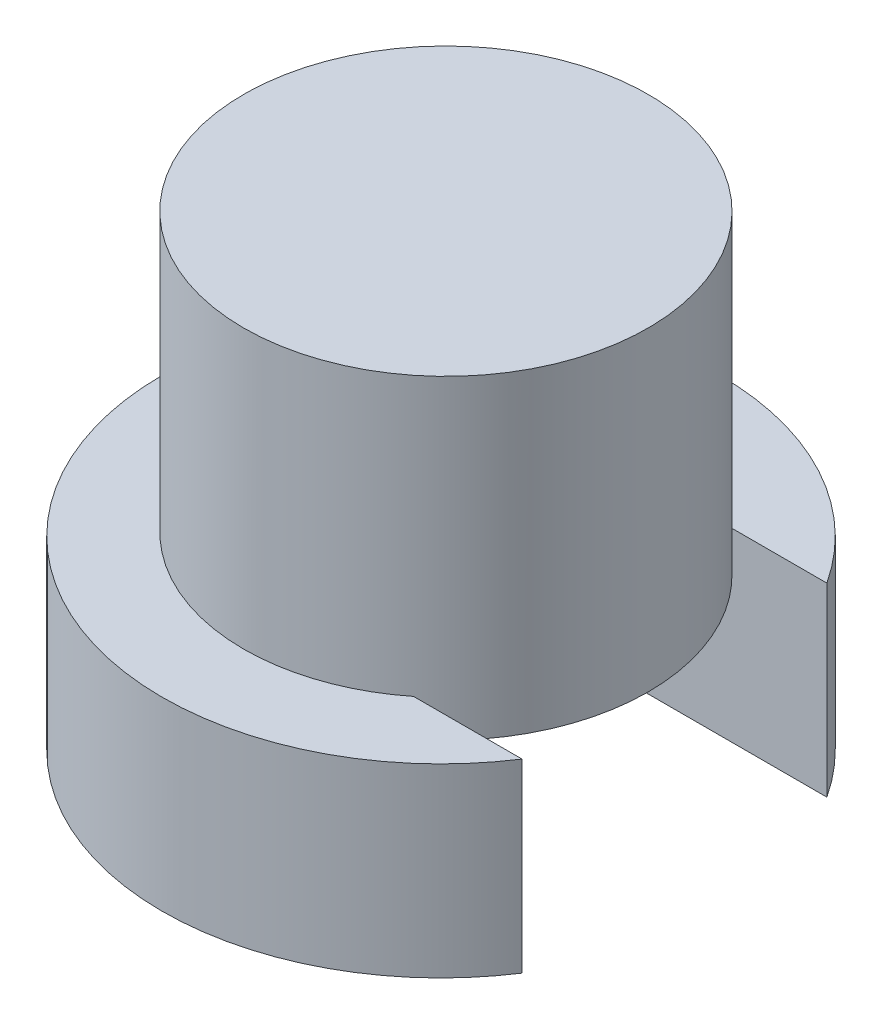
SolidWorks part; units mm, degrees
ref_plane "Front Plane" through (0, 0, 0) normal (0, 0, 1) x (1, 0, 0)
ref_plane "Top Plane" through (0, 0, 0) normal (0, 1, 0) x (1, 0, 0)
ref_plane "Right Plane" through (0, 0, 0) normal (1, 0, 0) x (0, 0, -1)
sketch "Sketch1" plane through (0, 0, 0) normal (0, 1, 0) x (1, 0, 0)
  line L1 (-21.3537, 0) -> (49.3226, 0)
  line L2 (-21.3537, 0) -> (-21.3537, 32.8817)
  line L3 (-21.3537, 32.8817) -> (49.3226, 32.8817)
  line L4 (49.3226, 0) -> (49.3226, 32.8817)
  circle A0 centre (-21.3537, 16.4409) radius 30.0747
extrude "Boss-Extrude1" add sketch "Sketch1" along normal blind 20 contours L3 A0 L1 L2 region at (-28.3845, 0, -16.4409)
ref_plane "Plane1" through (0, 50, 0) normal (0, 1, 0) x (1, 0, 0)
sketch "Sketch3" plane through (0, 50, 0) normal (0, 1, 0) x (1, 0, 0)
  circle A0 centre (-21.4618, 17.0803) radius 21.8254
extrude "Boss-Extrude2" add sketch "Sketch3" against normal blind 34 contours A0
